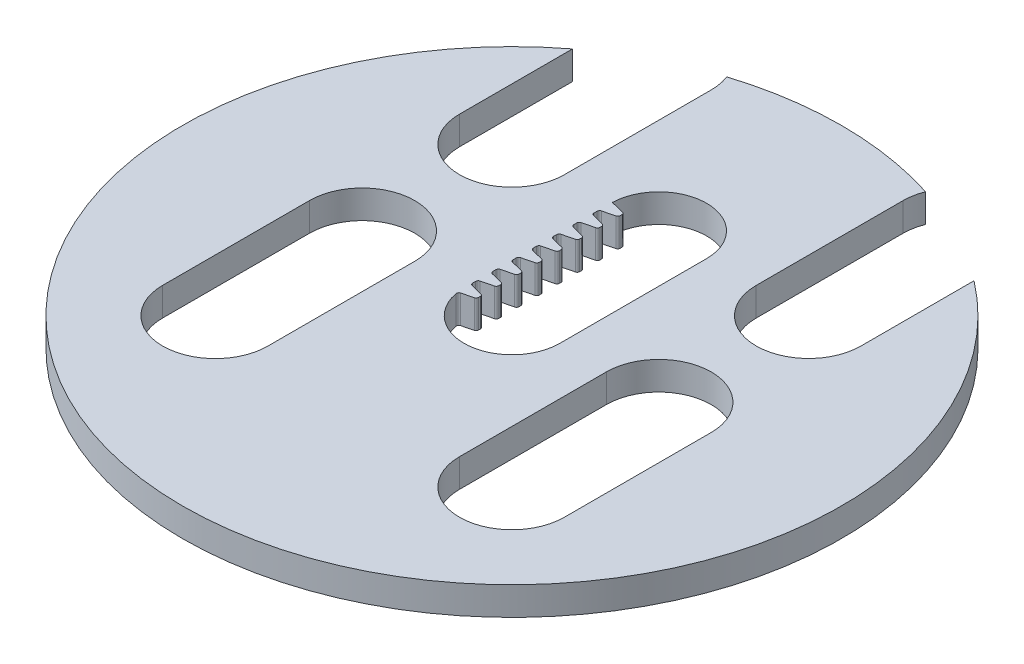
SolidWorks part; units mm, degrees
ref_plane "Front Plane" through (0, 0, 0) normal (0, 0, 1) x (1, 0, 0)
ref_plane "Top Plane" through (0, 0, 0) normal (0, 1, 0) x (1, 0, 0)
ref_plane "Right Plane" through (0, 0, 0) normal (1, 0, 0) x (0, 0, -1)
sketch "Sketch3" plane through (0, 0, 0) normal (0, -1, 0) x (1, 0, 0)
  line L0 (0, 0) -> (0, -17.78) construction
  line L1 (5.8, 0) -> (5.8, -17.78)
  line L2 (-5.8, 0) -> (-5.8, -17.78)
  line L3 (-17.9605, -35.7405) -> (17.9605, 0.1805) construction
  line L4 (-17.9605, 0.1805) -> (17.9605, -35.7405) construction
  line L5 (-17.9605, 0.1805) -> (17.9605, 0.1805) construction
  line L6 (-17.9605, 0.1805) -> (-17.9605, 17.9605) construction
  line L7 (-24.3305, 0.1805) -> (-24.3305, 17.9605)
  line L8 (-11.5905, 0.1805) -> (-11.5905, 17.9605)
  line L9 (-17.9605, -35.7405) -> (-17.9605, -17.9605) construction
  line L10 (-24.3105, -35.7405) -> (-24.3105, -17.9605)
  line L11 (-11.6105, -35.7405) -> (-11.6105, -17.9605)
  line L12 (17.9605, 0.1805) -> (17.9605, 17.9605) construction
  line L13 (11.6105, 0.1805) -> (11.6105, 17.9605)
  line L14 (24.3105, 0.1805) -> (24.3105, 17.9605)
  line L15 (17.9605, -35.7405) -> (17.9605, -17.9605) construction
  line L16 (11.6105, -35.7405) -> (11.6105, -17.9605)
  line L17 (24.3105, -35.7405) -> (24.3105, -17.9605)
  circle A0 centre (0, 0) radius 39.9034
  arc A1 (5.8, 0) -> (-5.8, 0) centre (0, 0) ccw
  arc A2 (-5.8, -17.78) -> (5.8, -17.78) centre (0, -17.78) ccw
  arc A3 (-24.3305, 0.1805) -> (-11.5905, 0.1805) centre (-17.9605, 0.1805) ccw
  arc A4 (-11.5905, 17.9605) -> (-24.3305, 17.9605) centre (-17.9605, 17.9605) ccw
  arc A5 (-24.3105, -35.7405) -> (-11.6105, -35.7405) centre (-17.9605, -35.7405) ccw
  arc A6 (-11.6105, -17.9605) -> (-24.3105, -17.9605) centre (-17.9605, -17.9605) ccw
  arc A7 (11.6105, 0.1805) -> (24.3105, 0.1805) centre (17.9605, 0.1805) ccw
  arc A8 (24.3105, 17.9605) -> (11.6105, 17.9605) centre (17.9605, 17.9605) ccw
  arc A9 (11.6105, -35.7405) -> (24.3105, -35.7405) centre (17.9605, -35.7405) ccw
  arc A10 (24.3105, -17.9605) -> (11.6105, -17.9605) centre (17.9605, -17.9605) ccw
  point P5 (0, -8.89)
  point P10 (-17.9605, 9.0705)
  point P13 (0, -17.78)
  point P16 (0, -17.78)
  point P22 (-17.9605, -26.8505)
  point P28 (17.9605, 9.0705)
  point P34 (17.9605, -26.8505)
  dimension "D1" = 79.8068
  dimension "D3" = 5.8
  dimension "D8" = 6.37
  dimension "D10" = 6.35
  dimension "D13" = 6.35
  dimension "D14" = 6.35
  dimension "D2" = 17.78
  dimension "D4" = 45
  dimension "D5" = 45
  dimension "D6" = 50.8
extrude "Boss-Extrude1" add sketch "Sketch3" along normal blind 3.175 and the other way blind 0.254 contours L17 A10 L16 A0 L11 A6 L10 L2 A2 L1 A1 L8 A4 L7 A3 L14 A8 L13 A7 region at (-17.1393, 0, 34.7811)
sketch "Sketch4" plane through (0, 0.254, 0) normal (0, 1, 0) x (1, 0, 0)
  line L0 (-5.8, 0) -> (-3.94, 0) construction
  line L1 (-3.94, -0.34) -> (-3.94, 0.34)
  line L2 (-3.94, 0.34) -> (-5.8, 0.8038)
  line L3 (-5.8, 0) -> (-5.8, 17.78) construction
  line L8 (-5.8, 0.8038) -> (-5.8, -0.8038)
  line L9 (-5.8, -0.8038) -> (-3.94, -0.34)
  point P7 (-3.94, 0)
  line M5 (-5.8, 0) -> (-5.8, 17.78)
  arc M8 (5.8, 0) -> (-5.8, 0) centre (0, 0) cw
  dimension "D3" = 76
  dimension "D1" = 1.86
  dimension "D2" = 0.34
extrude "Boss-Extrude2" add sketch "Sketch4" against normal up to surface (3.429 mm away) contours L1 L2 M5 M8 | L0 L9 L1 M8 | L8 L9 M8 region at (-4.9957, 0.254, -0.3016) region at (-5.7837, 0.254, 0.5979) region at (-4.9847, 0.254, 0.2975) up to face at (0, -3.175, -8.89)
pattern_linear "LPattern1" count 8 spacing 2.45 along (0, 0, -1) of "Boss-Extrude2"
fillet "Fillet1" radius 0.3 31 edges at (-3.94, -1.4605, 0.34) (-5.8, -1.4605, -1.6462) (-3.94, -1.4605, -2.11) (-3.94, -1.4605, -2.79) (-5.8, -1.4605, -3.2538) (-5.8, -1.4605, -4.0962) (-3.94, -1.4605, -4.56) (-3.94, -1.4605, -5.24) (-5.8, -1.4605, -5.7038) (-5.8, -1.4605, -6.5462) (-3.94, -1.4605, -7.01) (-3.94, -1.4605, -7.69) (-5.8, -1.4605, -8.1538) (-5.8, -1.4605, -8.9962) (-3.94, -1.4605, -9.46) (-3.94, -1.4605, -10.14) (-5.8, -1.4605, -10.6038) (-5.8, -1.4605, -11.4462) (-3.94, -1.4605, -11.91) (-3.94, -1.4605, -12.59) (-5.8, -1.4605, -13.0538) (-5.8, -1.4605, -13.8962) (-3.94, -1.4605, -14.36) (-3.94, -1.4605, -15.04) (-5.8, -1.4605, -15.5038) (-5.8, -1.4605, -16.3462) (-3.94, -1.4605, -16.81) (-3.94, -1.4605, -17.49) (-5.7459, -1.4605, 0.7903) (-5.8, -1.4605, -0.8038) (-3.94, -1.4605, -0.34)
equation "\"AIRFRAME_OD\"= 3.142in"
equation "\"AIRFRAME_ID\"= 3.00in"
equation "\"FLAT_T\"= 0.125in"
equation "\"COUPLER_OD\"= 2.998in"
equation "\"COUPLER_ID\"= 2.875in"
equation "\"NOSE_EXP_L\"= 3.5in"
equation "\"NOSE_SHOULDER_L\"= 1.5in"
equation "\"MAIN_L\"= 30in"
equation "\"RECO_COUP_L\"= 6in"
equation "\"RECO_SWITCH_L\"= 1.5in"
equation "\"RECO_ROD_X\"= 1.5in"
equation "\"DROGUE_L\"= 14in"
equation "\"ATS_FORE_COUP_L\"= 4in"
equation "\"ATS_AFT_COUP_L\"= 2.5in"
equation "\"ATS_ROD_X\"= 2in"
equation "\"LOWER_L\"= 16in"
equation "\"FIN_ROOT\"= 5in"
equation "\"FIN_X\"= 0.75in"
equation "\"FIN_N\"= 4"
equation "\"MOTOR_OD\"= 2.25in"
equation "\"MOTOR_ID\"= 2.126in"
equation "\"MOTOR_L\"= 8in"
equation "\"MOTOR_LOWER_X\"= 0.5in"
equation "\"CR_AFT_X\"= 0.5in"
equation "\"CR_FORE_X\"= 6in"
equation "\"D1@Boss-Extrude1\"=\"FLAT_T\""
equation "\"D1@Sketch3\"=\"AIRFRAME_OD\""
equation "\"D6@Sketch3\"=\"ATS_ROD_X\""
